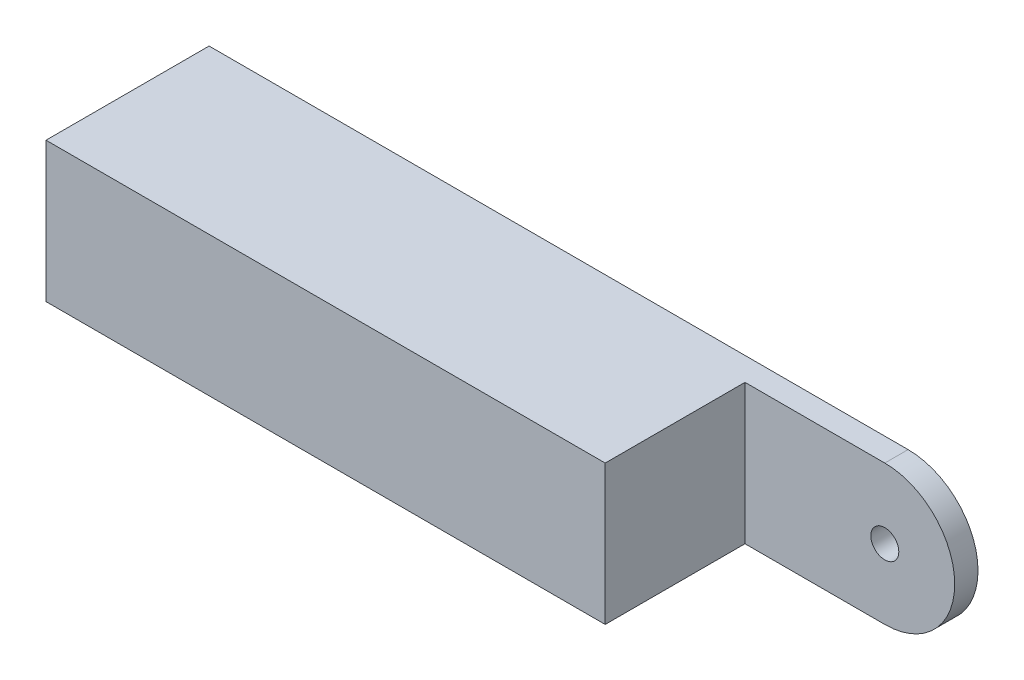
SolidWorks part; units mm, degrees
ref_plane "前视基准面" through (0, 0, 0) normal (0, 0, 1) x (1, 0, 0)
ref_plane "上视基准面" through (0, 0, 0) normal (0, 1, 0) x (1, 0, 0)
ref_plane "右视基准面" through (0, 0, 0) normal (1, 0, 0) x (0, 0, -1)
sketch "草图1" plane through (0, 0, 0) normal (0, 0, 1) x (1, 0, 0)
  line L1 (-60, 15) -> (60, 15)
  line L2 (-60, 15) -> (-60, -15)
  line L3 (-60, -15) -> (60, -15)
  line L4 (60, 15) -> (60, -15)
  line L7 (60, 15) -> (90, 15)
  line L8 (60, 15) -> (60, -15)
  line L9 (60, -15) -> (90, -15)
  arc A0 (90, 15) -> (90, -15) centre (90, 0) cw
  circle A1 centre (90, 0) radius 3
  point P0 (0, 0)
  dimension "D1" = 120
  dimension "D2" = 30
extrude "凸台-拉伸2" add sketch "草图1" along normal blind 35 contours L3 L4 L1 L2
extrude "凸台-拉伸3" add sketch "草图1<8>" along normal blind 5 contours A0 L7 L4 L9 A1 region at (80.8175, 0, 0)
sketch "草图1<8>" plane through (0, 0, 0) normal (0, 0, 1) x (1, 0, 0) same geometry as "草图1"
sketch "草图2" plane through (0, 0, 0) normal (0, 0, -1) x (-1, 0, 0)
  line L0 (60, 15) -> (60, -15) construction
  line L1 (10, 10) -> (50, 10)
  line L2 (10, 10) -> (10, -9.8838)
  line L3 (10, -9.8838) -> (50, -9.8838)
  line L4 (50, 10) -> (50, -9.8838)
  line L5 (60, 15) -> (-90, 15) construction
  dimension "D1" = 10
  dimension "D2" = 5
  dimension "D3" = 40
extrude "切除-拉伸1" cut sketch "草图2" against normal blind 30
sketch "草图3" plane through (0, 0, 5) normal (0, 0, 1) x (1, 0, 0)
  line L0 (90, 0) -> (105, 0) construction
  line L1 (105, 0) -> (68.8095, 0) construction
  line L2 (90, 15) -> (90, -15)
  arc A0 (90, -15) -> (90, 15) centre (90, 0) ccw construction
  point P12 (90, 0)
